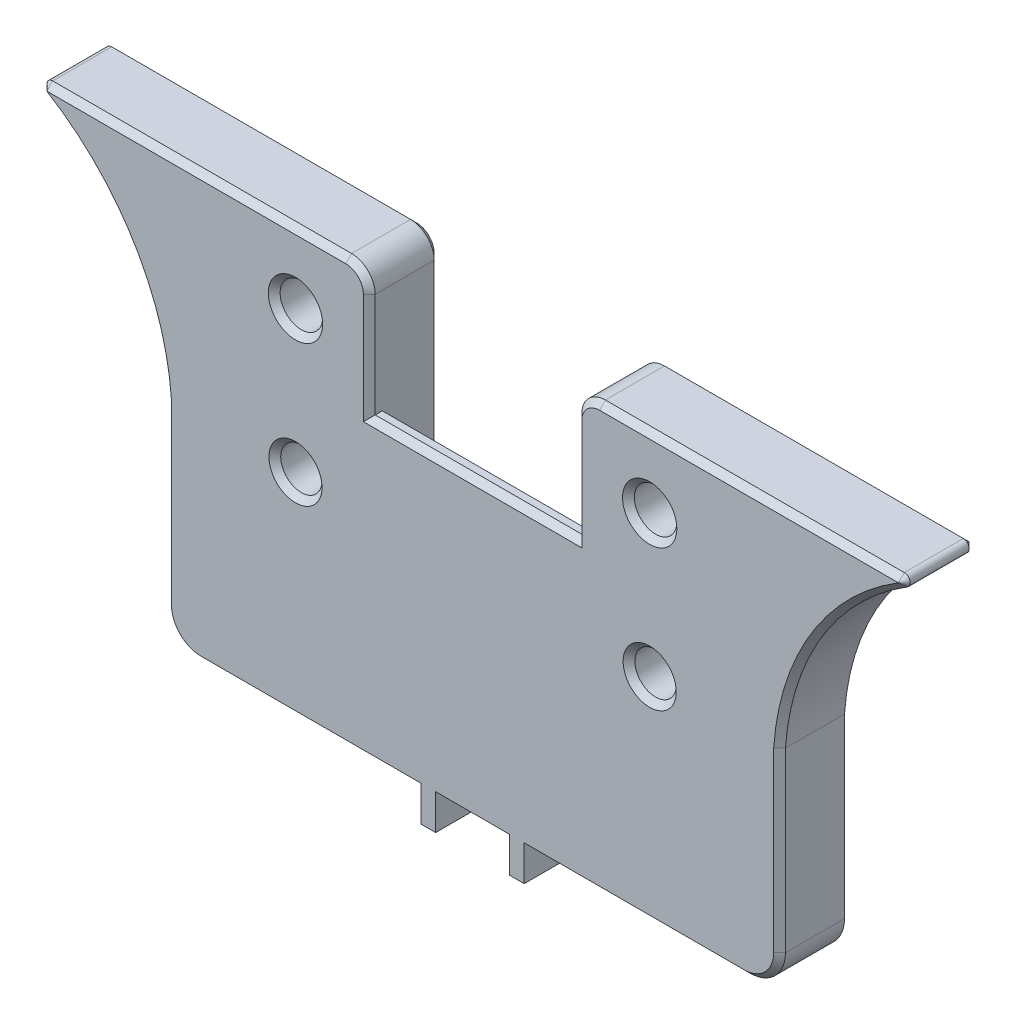
SolidWorks part; units mm, degrees
ref_plane "Front Plane" through (0, 0, 0) normal (0, 0, 1) x (1, 0, 0)
ref_plane "Top Plane" through (0, 0, 0) normal (0, 1, 0) x (1, 0, 0)
ref_plane "Right Plane" through (0, 0, 0) normal (1, 0, 0) x (0, 0, -1)
sketch "Sketch2" plane through (0, 0, 0) normal (0, 0, 1) x (1, 0, 0)
  line L0 (0, -33.2846) -> (0, 67.9981) construction
  line L12 (45.8007, 37.8996) -> (-45.8007, 37.8996)
  line L13 (-33.02, 15.1445) -> (-33.02, -3.9055)
  line L14 (-29.21, -7.7155) -> (29.21, -7.7155)
  line L15 (33.02, 15.1445) -> (33.02, -3.9055)
  circle A4 centre (-19.05, 15.1445) radius 2.2225
  circle A12 centre (19.05, 15.1445) radius 2.2225
  arc A13 (-33.02, 15.1445) -> (-46.1321, 36.723) centre (-60.5269, 13.203) ccw
  arc A14 (33.02, 15.1445) -> (46.1321, 36.723) centre (60.5269, 13.203) cw
  arc A15 (33.02, -3.9055) -> (29.21, -7.7155) centre (29.21, -3.9055) cw
  arc A16 (-33.02, -3.9055) -> (-29.21, -7.7155) centre (-29.21, -3.9055) ccw
  arc A17 (46.1321, 36.723) -> (45.8007, 37.8996) centre (45.8007, 37.2646) ccw
  arc A18 (-45.8007, 37.8996) -> (-46.1321, 36.723) centre (-45.8007, 37.2646) ccw
  point P4 (0, 57.6776)
  point P9 (0, 19.5776)
  point P12 (0, 37.8996)
  point P16 (0, -7.7155)
  point P18 (33.02, -7.7155)
  point P20 (0, -3.9055)
  point P22 (-33.02, -7.7155)
  point P27 (48.26, 37.8996)
  point P30 (-48.26, 37.8996)
  dimension "D2" = 48.26
  dimension "D3" = 22.86
  dimension "D6" = 0.635
  dimension "D4" = 33.02
  dimension "D5" = 3.81
  dimension "D7" = 27.5753
  dimension "D8" = 19.05
  dimension "D9" = 45.8007
  dimension "D10" = 19.05
  dimension "D11" = 19.5776
  dimension "D12" = 57.6776
  dimension "D1" = 4.445
extrude "Boss-Extrude1" add sketch "Sketch2" along normal blind 7.62
sketch "Sketch11" plane through (0, 0, 7.62) normal (0, 0, 1) x (1, 0, 0)
  line L0 (0, 41.9648) -> (0, -47.1588) construction
  line L1 (-19.05, 15.1445) -> (-19.05, 30.3845) construction
  circle A0 centre (-19.05, 30.3845) radius 2.286
  circle A1 centre (19.05, 30.3845) radius 2.286
  dimension "D2" = 4.572
  dimension "D1" = 15.24
extrude "Cut-Extrude9" cut sketch "Sketch11" against normal through all
sketch "Sketch12" plane through (0, 0, 0) normal (0, 0, 1) x (1, 0, 0)
  line L0 (0, 39.594) -> (0, -43.4023) construction
  line L1 (-4.7625, 33.4498) -> (4.7625, 33.4498)
  line L3 (4.7625, 10.9708) -> (-4.7625, 10.9708)
  line L4 (-11.1125, 17.3208) -> (-11.1125, 27.0998)
  line L5 (11.1125, 17.3208) -> (11.1125, 27.0998)
  arc A0 (11.1125, 27.0998) -> (4.7625, 33.4498) centre (4.7625, 27.0998) ccw
  arc A1 (11.1125, 17.3208) -> (4.7625, 10.9708) centre (4.7625, 17.3208) cw
  arc A2 (-4.7625, 10.9708) -> (-11.1125, 17.3208) centre (-4.7625, 17.3208) cw
  arc A3 (-4.7625, 33.4498) -> (-11.1125, 27.0998) centre (-4.7625, 27.0998) ccw
  point P10 (0, 10.9708)
  point P11 (0, 33.4498)
  point P13 (11.1125, 33.4498)
  point P16 (11.1125, 10.9708)
  point P19 (-11.1125, 10.9708)
  point P22 (-11.1125, 33.4498)
  dimension "D4" = 6.35
  dimension "D1" = 11.1125
  dimension "D2" = 10.9708
  dimension "D3" = 22.479
extrude "Cut-Extrude11" cut sketch "Sketch12" along normal blind 6.223
sketch "Sketch13" plane through (0, 0, 0) normal (0, 0, -1) x (-1, 0, 0)
  line L2 (-11.1125, 40.3062) -> (-11.1125, 24.1288)
  line L3 (-11.1125, 24.1288) -> (11.1125, 24.1288)
  line L7 (-11.1125, 40.3062) -> (11.1125, 40.3062)
  line L8 (11.1125, 40.3062) -> (11.1125, 24.1288)
  dimension "D1" = 11.1125
  dimension "D2" = 11.1125
  dimension "D3" = 24.1288
  dimension "D4" = 40.3062
extrude "Cut-Extrude12" cut sketch "Sketch13" against normal through all
sketch "Sketch15" plane through (0, -7.7155, 0) normal (0, -1, 0) x (1, 0, 0)
  line L0 (0, -11.1019) -> (0, 17.7532) construction
  line L1 (-29.21, 3.81) -> (29.21, 3.81) construction
  line L4 (-29.21, 7.62) -> (-29.21, 0) construction
  line L5 (29.21, 7.62) -> (29.21, 0) construction
  circle A0 centre (0, 3.81) radius 2.032
  dimension "D1" = 4.064
extrude "Cut-Extrude14" cut sketch "Sketch15" against normal blind 17.78
sketch "Sketch16" plane through (0, 0, 0) normal (0, 0, -1) x (-1, 0, 0)
  line L0 (29.21, -7.7155) -> (-29.21, -7.7155) construction
  line L1 (-3.9687, -7.7155) -> (-5.5563, -7.7155)
  line L2 (-3.9687, -7.7155) -> (-3.9688, -10.8905)
  line L3 (-3.9688, -10.8905) -> (-5.5563, -10.8905)
  line L4 (-5.5563, -7.7155) -> (-5.5563, -10.8905)
  line L5 (0, -11.3212) -> (0, 10.1435) construction
  line L6 (5.5562, -7.7155) -> (3.9688, -7.7155)
  line L7 (5.5562, -7.7155) -> (5.5562, -10.8905)
  line L8 (5.5562, -10.8905) -> (3.9688, -10.8905)
  line L9 (3.9688, -7.7155) -> (3.9688, -10.8905)
  dimension "D1" = 1.5875
  dimension "D2" = 3.175
  dimension "D3" = 7.9375
  dimension "D4" = 3.9688
extrude "Boss-Extrude2" add sketch "Sketch16" against normal up to surface (7.62 mm away) up to face at (-16.764, 30.3845, 7.62)
fillet "Fillet1" radius 2.54 2 edges at (11.1125, 37.8996, 3.81) (-11.1125, 37.8996, 3.81)
chamfer "Chamfer1" distance 0.635 angle 45 46 edges at (-16.8275, 15.1445, 0) (-16.8275, 15.1445, 7.62) (-16.764, 30.3845, 7.62) (-16.764, 30.3845, 0) (16.764, 30.3845, 7.62) (16.764, 30.3845, 0) (16.8275, 15.1445, 0) (16.8275, 15.1445, 7.62) (0, -7.7155, 0) (11.1125, 26.3402, 0) (9.2526, 12.8307, 0) (0, 10.9708, 0) (-9.2526, 12.8307, 0) (-11.1125, 26.3402, 0) (17.3831, -7.7155, 0) (33.02, 5.6195, 0) (31.9041, -6.5996, 0) (29.7266, 37.8996, 0) (46.4119, 37.4368, 0) (36.9611, 27.5227, 0) (-17.3831, -7.7155, 0) (-29.7266, 37.8996, 0) (-31.9041, -6.5996, 0) (-46.4119, 37.4368, 0) (-33.02, 5.6195, 0) (-36.9611, 27.5227, 0) (-33.02, 5.6195, 7.62) (-31.9041, -6.5996, 7.62) (-17.3831, -7.7155, 7.62) (0, -7.7155, 7.62) (17.3831, -7.7155, 7.62) (31.9041, -6.5996, 7.62) (33.02, 5.6195, 7.62) (-36.9611, 27.5227, 7.62) (36.9611, 27.5227, 7.62) (-46.4119, 37.4368, 7.62) (46.4119, 37.4368, 7.62) (-29.7266, 37.8996, 7.62) (29.7266, 37.8996, 7.62) (11.1125, 29.7442, 7.62) (0, 24.1288, 7.62) (-11.1125, 29.7442, 7.62) (11.8564, 37.1556, 0) (-11.8564, 37.1556, 0) (11.8564, 37.1556, 7.62) (-11.8564, 37.1556, 7.62)
equation "\"D4@Sketch16\"=\"D3@Sketch16\"/2"
